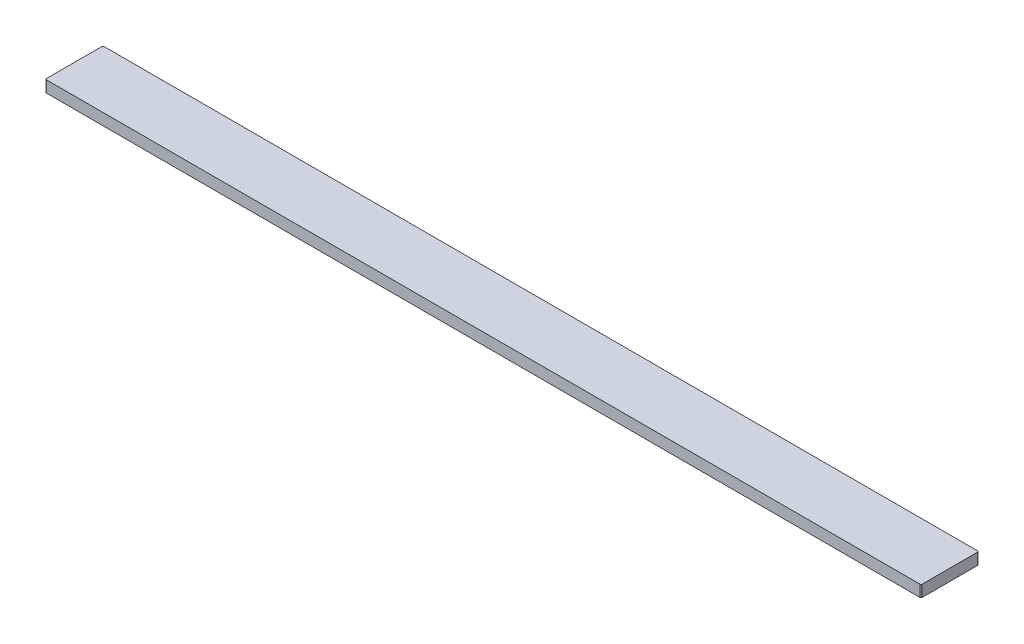
SolidWorks part; units mm, degrees
material "MS-Grade 400"
ref_plane "Front Plane" through (0, 0, 0) normal (0, 0, 1) x (1, 0, 0)
ref_plane "Top Plane" through (0, 0, 0) normal (0, 1, 0) x (1, 0, 0)
ref_plane "Right Plane" through (0, 0, 0) normal (1, 0, 0) x (0, 0, -1)
sketch "Sketch1" plane through (0, 0, 0) normal (0, 1, 0) x (1, 0, 0)
  line L1 (-380, 50) -> (380, 50)
  line L2 (-380, 50) -> (-380, 0)
  line L3 (-380, 0) -> (380, 0)
  line L4 (380, 50) -> (380, 0)
  dimension "D1" = 760
  dimension "D2" = 50
sheet metal parameters "Sheet-Metal1" thickness 10 parameters "D1"=92
base flange "Base-Flange1" sketch "Sketch1" thickness 10 reverse thickness direction no parameters "D1"=92
fillet "Fillet-1.0" radius 1 4 edges at (380, -5, -50) (380, -5, 0) (-380, -5, -50) (-380, -5, 0)
flat pattern "Flat-Pattern1" [suppressed]
sketch "Bend-Lines1" plane through (0, 0, 0) normal (0, 1, 0) x (1, 0, 0)
sketch3d "Bounding-Box1" [suppressed]
  line L0 (375, 0, 0) -> (-375, 0, 0) construction
  line L1 (375, 50, 0) -> (-375, 50, 0) construction
  line L2 (375, 0, 0) -> (375, 50, 0) construction
  line L3 (-375, 0, 0) -> (-375, 50, 0) construction
